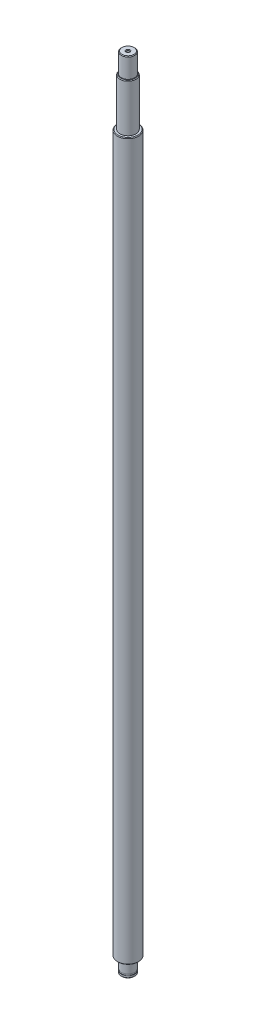
SolidWorks part; units mm, degrees
material "Chrome Stainless Steel"
ref_plane "Front Plane" through (0, 0, 0) normal (0, 0, 1) x (1, 0, 0)
ref_plane "Top Plane" through (0, 0, 0) normal (0, 1, 0) x (1, 0, 0)
ref_plane "Right Plane" through (0, 0, 0) normal (1, 0, 0) x (0, 0, -1)
sketch "Sketch1" plane through (0, 0, 0) normal (0, 0, 1) x (1, 0, 0)
  line L0 (0, 0) -> (0, -600) construction
  line L1 (0, 0) -> (-5, 0) construction
  line L2 (0, -15) -> (-6, -15) construction
  line L3 (-5, 0) -> (-5, -600) construction
  line L4 (-6, -15) -> (-6, -51) construction
  line L5 (0, -51) -> (-8, -51) construction
  line L6 (-8, -51) -> (-8, -589)
  line L7 (-8, -51) -> (-6, -51)
  line L8 (-6, -51) -> (-6, -15)
  line L9 (-6, -15) -> (-5, -15)
  line L10 (-5, -600) -> (0, -600) construction
  line L11 (-5, 0) -> (-1, 0)
  line L12 (-5, -15) -> (-5, 0)
  line L13 (-8, -589) -> (0, -589) construction
  line L14 (-8, -589) -> (-5, -589)
  line L15 (-5, -589) -> (-5, -597)
  line L16 (-5, -600) -> (-1, -600)
  line L17 (0, -3) -> (0, -597)
  line L18 (-4.8, 0) -> (-4.8, -600) construction
  line L19 (-5, -597) -> (0, -597) construction
  line L20 (-5, -598.15) -> (0, -598.15) construction
  line L21 (-5, -597) -> (-4.8, -597)
  line L22 (-4.8, -597) -> (-4.8, -598.15)
  line L23 (-4.8, -598.15) -> (-5, -598.15)
  line L24 (-5, -598.15) -> (-5, -600)
  line L25 (-1, 0) -> (-1, -600) construction
  line L26 (-1, 0) -> (-1, -3)
  line L27 (-1, -3) -> (0, -3)
  line L28 (0, -100) -> (-8, -100) construction
  line L29 (0, -597) -> (-1, -597)
  line L30 (-1, -597) -> (-1, -600)
  dimension "Length" = 600
  dimension "D2" = 5
  dimension "D3" = 15
  dimension "D4" = 6
  dimension "D5" = 36
  dimension "D6" = 8
  dimension "D7" = 11
  dimension "D8" = 4.8
  dimension "D9" = 1.15
  dimension "D10" = 9.15
  dimension "D11" = 1
  dimension "D12" = 3
  dimension "D13" = 3
revolve "Revolve1" add sketch "Sketch1" angle 360 about L17
chamfer "Chamfer1" distance 0.5 angle 45 5 edges at (-8, -589, 0) (-8, -51, 0) (-6, -15, 0) (-5, 0, 0) (-5, -600, 0)
chamfer "Chamfer2" distance 0.5 angle 30 4 edges at (-1, -597, 0) (-1, -600, 0) (-1, 0, 0) (-1, -3, 0) first distance on face at (-1, -597, 0) first distance on face at (-4.5, 0, 0) first distance on face at (-1, 0, 0)
ref_plane "Plane1" through (0, -14, 0) normal (0, 1, 0) x (-1, 0, 0)
ref_plane "Plane2" through (0, -26, 0) normal (0, 1, 0) x (-1, 0, 0)
ref_plane "Plane3" through (0, -48.25, 0) normal (0, 1, 0) x (-1, 0, 0)
sketch "Sketch4" plane through (0, -26, 0) normal (0, 1, 0) x (-1, 0, 0)
  circle A0 centre (0, 0) radius 6
  dimension "D1" = 12
curve "Helix/Spiral2"
sketch "Sketch2" plane through (0, -14, 0) normal (0, 1, 0) x (-1, 0, 0)
  circle A0 centre (0, 0) radius 6
  dimension "D1" = 12
curve "Helix/Spiral1" pitch 1 height 12 turns 12
sketch "Sketch3" plane through (0, 0, 0) normal (0, 0, 1) x (1, 0, 0)
  line L0 (-5, -13.52) -> (-6, -13.52) construction
  line L1 (-6, -14) -> (-5, -14) construction
  line L2 (-6, -14) -> (-6, -13.04) construction
  line L3 (-6, -13.04) -> (-5, -13.04) construction
  line L4 (-5, -14) -> (-5, -13.04) construction
  line L5 (-5.885, -13.885) -> (-5.115, -13.635)
  line L6 (-5.885, -13.155) -> (-5.115, -13.405)
  line L7 (-6, -13.04) -> (-6, -14)
  arc A0 (-5.115, -13.635) -> (-5.115, -13.405) centre (-5.115, -13.52) ccw
  arc A1 (-5.885, -13.885) -> (-6, -14) centre (-5.885, -14) ccw
  arc A2 (-5.885, -13.155) -> (-6, -13.04) centre (-5.885, -13.04) cw
  spline S0 degree 3 poles (-6, -14) (-6, -14.0207) (-5.6876, -14.0626) (-4.3531, -14.125) (-2.3559, -14.1875) (0, -14.25) (2.3559, -14.3125) (4.3531, -14.375) (5.6876, -14.4375) (6.1562, -14.5) (5.6876, -14.5625) (4.3531, -14.625) (2.3559, -14.6875) (0, -14.75) (-2.3559, -14.8125) (-4.3531, -14.875) (-5.6876, -14.9375) (-6.1562, -15) (-5.6876, -15.0625) (-4.3531, -15.125) (-2.3559, -15.1875) (0, -15.25) (2.3559, -15.3125) (4.3531, -15.375) (5.6876, -15.4375) (6.1562, -15.5) (5.6876, -15.5625) (4.3531, -15.625) (2.3559, -15.6875) (0, -15.75) (-2.3559, -15.8125) (-4.3531, -15.875) (-5.6876, -15.9375) (-6.1562, -16) (-5.6876, -16.0625) (-4.3531, -16.125) (-2.3559, -16.1875) (0, -16.25) (2.3559, -16.3125) (4.3531, -16.375) (5.6876, -16.4375) (6.1562, -16.5) (5.6876, -16.5625) (4.3531, -16.625) (2.3559, -16.6875) (0, -16.75) (-2.3559, -16.8125) (-4.3531, -16.875) (-5.6876, -16.9375) (-6.1562, -17) (-5.6876, -17.0625) (-4.3531, -17.125) (-2.3559, -17.1875) (0, -17.25) (2.3559, -17.3125) (4.3531, -17.375) (5.6876, -17.4375) (6.1562, -17.5) (5.6876, -17.5625) (4.3531, -17.625) (2.3559, -17.6875) (0, -17.75) (-2.3559, -17.8125) (-4.3531, -17.875) (-5.6876, -17.9375) (-6.1562, -18) (-5.6876, -18.0625) (-4.3531, -18.125) (-2.3559, -18.1875) (0, -18.25) (2.3559, -18.3125) (4.3531, -18.375) (5.6876, -18.4375) (6.1562, -18.5) (5.6876, -18.5625) (4.3531, -18.625) (2.3559, -18.6875) (0, -18.75) (-2.3559, -18.8125) (-4.3531, -18.875) (-5.6876, -18.9375) (-6.1562, -19) (-5.6876, -19.0625) (-4.3531, -19.125) (-2.3559, -19.1875) (0, -19.25) (2.3559, -19.3125) (4.3531, -19.375) (5.6876, -19.4375) (6.1562, -19.5) (5.6876, -19.5625) (4.3531, -19.625) (2.3559, -19.6875) (0, -19.75) (-2.3559, -19.8125) (-4.3531, -19.875) (-5.6876, -19.9375) (-6.1562, -20) (-5.6876, -20.0625) (-4.3531, -20.125) (-2.3559, -20.1875) (0, -20.25) (2.3559, -20.3125) (4.3531, -20.375) (5.6876, -20.4375) (6.1562, -20.5) (5.6876, -20.5625) (4.3531, -20.625) (2.3559, -20.6875) (0, -20.75) (-2.3559, -20.8125) (-4.3531, -20.875) (-5.6876, -20.9375) (-6.1562, -21) (-5.6876, -21.0625) (-4.3531, -21.125) (-2.3559, -21.1875) (0, -21.25) (2.3559, -21.3125) (4.3531, -21.375) (5.6876, -21.4375) (6.1562, -21.5) (5.6876, -21.5625) (4.3531, -21.625) (2.3559, -21.6875) (0, -21.75) (-2.3559, -21.8125) (-4.3531, -21.875) (-5.6876, -21.9375) (-6.1562, -22) (-5.6876, -22.0625) (-4.3531, -22.125) (-2.3559, -22.1875) (0, -22.25) (2.3559, -22.3125) (4.3531, -22.375) (5.6876, -22.4375) (6.1562, -22.5) (5.6876, -22.5625) (4.3531, -22.625) (2.3559, -22.6875) (0, -22.75) (-2.3559, -22.8125) (-4.3531, -22.875) (-5.6876, -22.9375) (-6.1562, -23) (-5.6876, -23.0625) (-4.3531, -23.125) (-2.3559, -23.1875) (0, -23.25) (2.3559, -23.3125) (4.3531, -23.375) (5.6876, -23.4375) (6.1562, -23.5) (5.6876, -23.5625) (4.3531, -23.625) (2.3559, -23.6875) (0, -23.75) (-2.3559, -23.8125) (-4.3531, -23.875) (-5.6876, -23.9375) (-6.1562, -24) (-5.6876, -24.0625) (-4.3531, -24.125) (-2.3559, -24.1875) (0, -24.25) (2.3559, -24.3125) (4.3531, -24.375) (5.6876, -24.4375) (6.1562, -24.5) (5.6876, -24.5625) (4.3531, -24.625) (2.3559, -24.6875) (0, -24.75) (-2.3559, -24.8125) (-4.3531, -24.875) (-5.6876, -24.9375) (-6.1562, -25) (-5.6876, -25.0625) (-4.3531, -25.125) (-2.3559, -25.1875) (0, -25.25) (2.3559, -25.3125) (4.3531, -25.375) (5.6876, -25.4375) (6.1562, -25.5) (5.6876, -25.5625) (4.3531, -25.625) (2.3559, -25.6875) (0, -25.75) (-2.3559, -25.8125) (-4.3531, -25.875) (-5.6876, -25.9374) (-6, -25.9793) (-6, -26) knots 0 0 0 0 0.005208 0.010417 0.015625 0.020833 0.026042 0.03125 0.036458 0.041667 0.046875 0.052083 0.057292 0.0625 0.067708 0.072917 0.078125 0.083333 0.088542 0.09375 0.098958 0.104167 0.109375 0.114583 0.119792 0.125 0.130208 0.135417 0.140625 0.145833 0.151042 0.15625 0.161458 0.166667 0.171875 0.177083 0.182292 0.1875 0.192708 0.197917 0.203125 0.208333 0.213542 0.21875 0.223958 0.229167 0.234375 0.239583 0.244792 0.25 0.255208 0.260417 0.265625 0.270833 0.276042 0.28125 0.286458 0.291667 0.296875 0.302083 0.307292 0.3125 0.317708 0.322917 0.328125 0.333333 0.338542 0.34375 0.348958 0.354167 0.359375 0.364583 0.369792 0.375 0.380208 0.385417 0.390625 0.395833 0.401042 0.40625 0.411458 0.416667 0.421875 0.427083 0.432292 0.4375 0.442708 0.447917 0.453125 0.458333 0.463542 0.46875 0.473958 0.479167 0.484375 0.489583 0.494792 0.5 0.505208 0.510417 0.515625 0.520833 0.526042 0.53125 0.536458 0.541667 0.546875 0.552083 0.557292 0.5625 0.567708 0.572917 0.578125 0.583333 0.588542 0.59375 0.598958 0.604167 0.609375 0.614583 0.619792 0.625 0.630208 0.635417 0.640625 0.645833 0.651042 0.65625 0.661458 0.666667 0.671875 0.677083 0.682292 0.6875 0.692708 0.697917 0.703125 0.708333 0.713542 0.71875 0.723958 0.729167 0.734375 0.739583 0.744792 0.75 0.755208 0.760417 0.765625 0.770833 0.776042 0.78125 0.786458 0.791667 0.796875 0.802083 0.807292 0.8125 0.817708 0.822917 0.828125 0.833333 0.838542 0.84375 0.848958 0.854167 0.859375 0.864583 0.869792 0.875 0.880208 0.885417 0.890625 0.895833 0.901042 0.90625 0.911458 0.916667 0.921875 0.927083 0.932292 0.9375 0.942708 0.947917 0.953125 0.958333 0.963542 0.96875 0.973958 0.979167 0.984375 0.989583 0.994792 1 1 1 1 construction
  dimension "D3" = 0.23
  dimension "D1" = 1
  dimension "D2" = 0.96
sweep "Cut-Sweep1" [suppressed] cut profiles "Sketch3" path "Helix/Spiral1"
sketch "Sketch5" [suppressed] plane through (0, 0, 0) normal (0, 0, 1) x (1, 0, 0)
  line L3 (-6, -25.04) -> (-6, -26)
  line L4 (-5.885, -25.885) -> (-5.115, -25.635)
  line L5 (-5.115, -25.405) -> (-5.885, -25.155)
  line L6 (-6, -25.04) -> (-6, -26)
  line L7 (-5.885, -25.885) -> (-5.115, -25.635)
  line L8 (-5.115, -25.405) -> (-5.885, -25.155)
  arc A3 (-6, -25.04) -> (-5.885, -25.155) centre (-5.885, -25.04) ccw
  arc A4 (-5.885, -25.885) -> (-6, -26) centre (-5.885, -26) ccw
  arc A5 (-5.115, -25.635) -> (-5.115, -25.405) centre (-5.115, -25.52) ccw
  arc A6 (-6, -25.04) -> (-5.885, -25.155) centre (-5.885, -25.04) ccw
  arc A7 (-5.885, -25.885) -> (-6, -26) centre (-5.885, -26) ccw
  arc A8 (-5.115, -25.635) -> (-5.115, -25.405) centre (-5.115, -25.52) ccw
  dimension "D1" = 0
sweep "Cut-Sweep2" [suppressed] cut profiles "Sketch5" path "Helix/Spiral2"
sketch "Sketch6" plane through (0, -48.25, 0) normal (0, 1, 0) x (-1, 0, 0)
  circle A0 centre (0, 0) radius 8
  dimension "D1" = 16
curve "Helix/Spiral3" pitch 5 height 543 turns 108.6 parameters "Thread"=543, "Pitch"=5
sketch "Sketch7" plane through (0, 0, 0) normal (0, 0, 1) x (1, 0, 0)
  line L0 (-8, -48.255) -> (-8, -50.655) construction
  line L1 (0, 0) -> (0, -48.255) construction
  line L2 (0, -48.255) -> (-8, -48.255) construction
  line L4 (-8, -50.655) -> (-7.1, -50.655)
  line L5 (-8, -50.655) -> (-8, -50.855)
  line L6 (-8, -50.855) -> (-7.1, -50.855)
  line L7 (-7.1, -50.655) -> (-7.1, -50.855)
  circle A0 centre (-8, -48.255) radius 1.9
  dimension "D2" = 48.255
  dimension "D1" = 3.8
  dimension "D3" = 0.9
  dimension "D4" = 0.9
  dimension "D5" = 0.2
  dimension "D6" = 2.4
  dimension "D7" = 8
sweep "Cut-Sweep3" [suppressed] cut profiles "Sketch7" path "Helix/Spiral3"
equation "\"Thread@Helix/Spiral3\"=(\"Length@Sketch1\"-57)"
